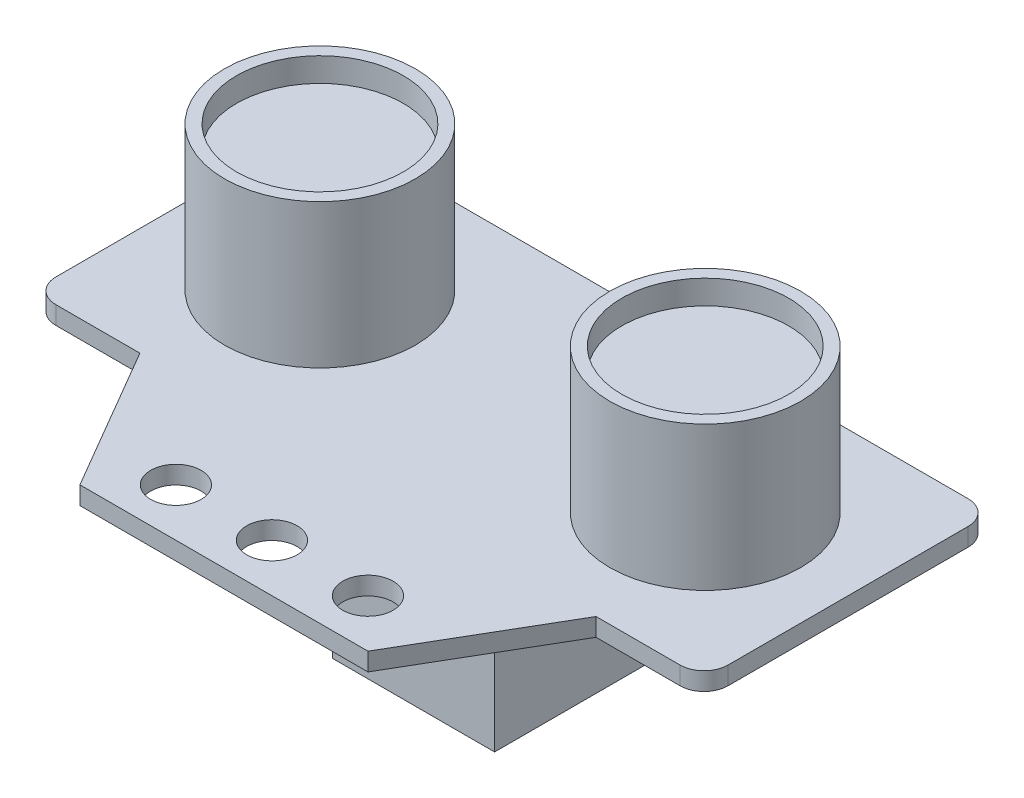
SolidWorks part; units mm, degrees
ref_plane "Front Plane" through (0, 0, 0) normal (0, 0, 1) x (1, 0, 0)
ref_plane "Top Plane" through (0, 0, 0) normal (0, 1, 0) x (1, 0, 0)
ref_plane "Right Plane" through (0, 0, 0) normal (1, 0, 0) x (0, 0, -1)
sketch "Sketch1" plane through (0, 0, 0) normal (0, 1, 0) x (1, 0, 0)
  line L0 (12, 0) -> (-12, 0)
  line L1 (-12, 0) -> (-19, 12)
  line L2 (-19, 12) -> (-28, 12)
  line L3 (-28, 12) -> (-28, 36)
  line L4 (-28, 36) -> (28, 36)
  line L5 (0, 36) -> (0, 0) construction
  line L6 (28, 12) -> (28, 36)
  line L7 (19, 12) -> (28, 12)
  line L8 (12, 0) -> (19, 12)
  line L9 (-8, 4) -> (8, 4) construction
  circle A0 centre (0, 4) radius 2.1
  circle A1 centre (-8, 4) radius 2.1
  circle A2 centre (8, 4) radius 2.1
  dimension "D6" = 4.2
  dimension "D1" = 56
  dimension "D2" = 36
  dimension "D3" = 24
  dimension "D4" = 24
  dimension "D5" = 9
  dimension "D7" = 1.9
  dimension "D8" = 16
extrude "Boss-Extrude1" add sketch "Sketch1" along normal blind 1.5
fillet "Fillet1" radius 2 4 edges at (28, 0.75, -12) (28, 0.75, -36) (-28, 0.75, -36) (-28, 0.75, -12)
sketch "Sketch2" plane through (0, 1.5, 0) normal (0, 1, 0) x (1, 0, 0)
  line L0 (0, 0) -> (0, 36) construction
  line L1 (26, 36) -> (-26, 36) construction
  line L2 (-28, 34) -> (-28, 14) construction
  circle A0 centre (-16.05, 24.05) radius 7.95
  circle A1 centre (16.05, 24.05) radius 7.95
  dimension "D1" = 15.9
  dimension "D2" = 4
  dimension "D3" = 4
extrude "Boss-Extrude2" add sketch "Sketch2" along normal blind 12
sketch "Sketch3" plane through (0, 0, 0) normal (0, -1, 0) x (1, 0, 0)
  line L0 (26, -36) -> (-26, -36) construction
  line L1 (-6.75, -15.8) -> (6.75, -15.8)
  line L2 (-6.75, -15.8) -> (-6.75, -31.8)
  line L3 (-6.75, -31.8) -> (6.75, -31.8)
  line L4 (6.75, -15.8) -> (6.75, -31.8)
  point P4 (0, -15.8)
  dimension "D1" = 13.5
  dimension "D2" = 16
  dimension "D3" = 4.2
extrude "Boss-Extrude3" add sketch "Sketch3" along normal blind 16.3
sketch "Sketch4" plane through (0, 13.5, 0) normal (0, 1, 0) x (1, 0, 0)
  circle A3 centre (-16.05, 24.05) radius 6.95
  circle A4 centre (-16.05, 24.05) radius 6.95
  circle A6 centre (16.05, 24.05) radius 6.95
  circle A7 centre (16.05, 24.05) radius 6.95
  dimension "D1" = 1
  dimension "D2" = 1
extrude "Cut-Extrude1" cut sketch "Sketch4" against normal blind 2
equation "\"width\"= 24"
equation "\"thk\"= 3"
equation "\"holesize\"= 4.2"
equation "\"holedistance\"= ( 20 + 12 ) / 2"
equation "\"threaded_hole\"= 3.9"
equation "\"fillet_radius\"= 2"
equation "\"ground_clearance\"= 25"
equation "\"tire_thk\"= 3"
equation "\"innerwheel_diam\"= \"wheel_diam\"-2*\"tire_thk\""
equation "\"innerwheel_thk\"= 8"
equation "\"wheel_diam\"= 2*(\"width\"/2+\"ground_clearance\")"
equation "\"D6@Sketch1\"=\"holesize\""
equation "\"D8@Sketch1\"=\"holedistance\""
